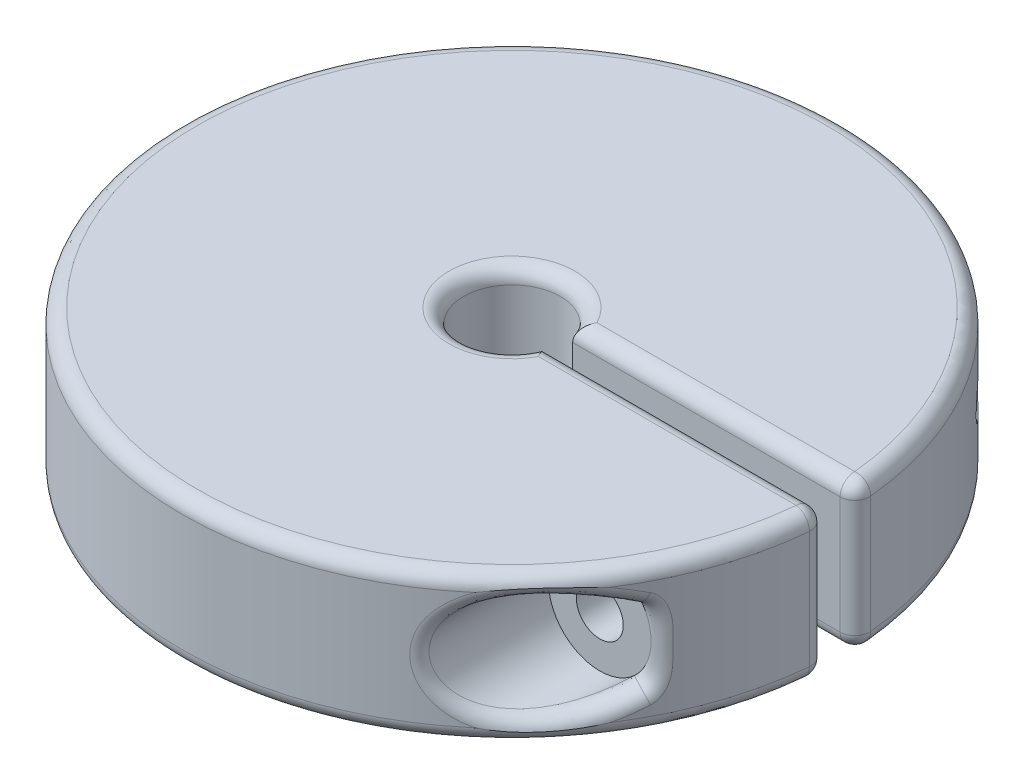
SolidWorks part; units mm, degrees
ref_plane "Front Plane" through (0, 0, 0) normal (0, 0, 1) x (1, 0, 0)
ref_plane "Top Plane" through (0, 0, 0) normal (0, 1, 0) x (1, 0, 0)
ref_plane "Right Plane" through (0, 0, 0) normal (1, 0, 0) x (0, 0, -1)
sketch "Sketch1" plane through (0, 0, 0) normal (0, 1, 0) x (1, 0, 0)
  circle A0 centre (0, 0) radius 22.5
  circle A1 centre (0, 0) radius 3.3
extrude "Boss-Extrude1" add sketch "Sketch1" along normal blind 10
sketch "Sketch2" plane through (0, 10, 0) normal (0, 1, 0) x (1, 0, 0)
  line L1 (0, 1) -> (24.0124, 1)
  line L2 (0, 1) -> (0, -1)
  line L3 (0, -1) -> (24.0124, -1)
  line L4 (24.0124, 1) -> (24.0124, -1)
extrude "Cut-Extrude1" cut sketch "Sketch2" against normal through all
ref_plane "Plane1" through (0, 0, 29) normal (0, 0, 1) x (1, 0, 0)
sketch "Sketch4" plane through (0, 0, 29) normal (0, 0, 1) x (1, 0, 0)
  circle A0 centre (16, 5) radius 1.25
extrude "Cut-Extrude2" cut sketch "Sketch4" against normal through all
sketch "Sketch5" plane through (0, 0, 29) normal (0, 0, 1) x (1, 0, 0)
  circle A0 centre (16, 5) radius 1.6
extrude "Cut-Extrude3" cut sketch "Sketch5" against normal blind 29
sketch "Sketch6" plane through (0, 0, 29) normal (0, 0, 1) x (1, 0, 0)
  circle A0 centre (16, 5) radius 3.5
extrude "Cut-Extrude4" cut sketch "Sketch6" against normal blind 19
fillet "Fillet1" radius 1 11 edges at (12.8113, 0, 1) (-3.3, 0, 0) (12.8113, 0, -1) (-22.5, 0, 0) (-3.3, 10, 0) (12.8113, 10, 1) (-22.5, 10, 0) (12.8113, 10, -1) (12.5263, 5.428, 18.6907) (22.4778, 5, 1) (22.4778, 5, -1)
